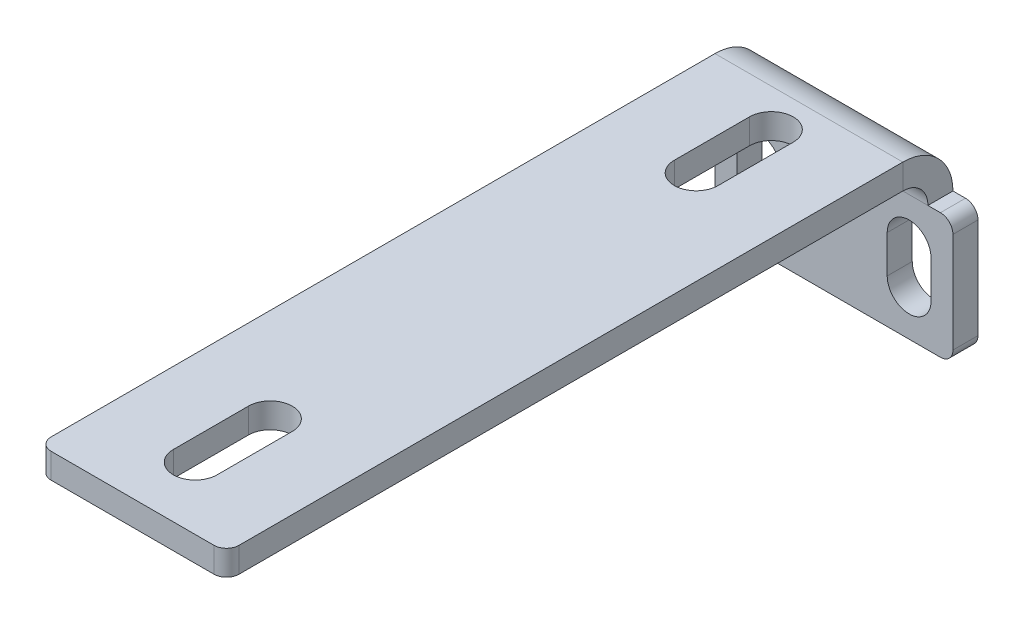
SolidWorks part; units mm, degrees
note: The reader was unsure of these and kept them because the rebuilt part matched: thickness of "Brida base1", "Brida de arista1", "Chapa metálica4", "Chapa metálica5", "Chapa metálica6"; flange length of "Brida de arista1".
material "aluminio"
ref_plane "Alzado" through (0, 0, 0) normal (0, 0, 1) x (1, 0, 0)
ref_plane "Planta" through (0, 0, 0) normal (0, 1, 0) x (1, 0, 0)
ref_plane "Vista lateral" through (0, 0, 0) normal (1, 0, 0) x (0, 0, -1)
sketch "Croquis1" plane through (0, 0, 0) normal (0, 0, 1) x (1, 0, 0)
  line L0 (0, -5) -> (9.5, -5) construction
  line L1 (0, 0) -> (19, 0)
  line L2 (0, 0) -> (0, -10)
  line L3 (0, -10) -> (19, -10)
  line L4 (19, 0) -> (19, -10)
  line L5 (9.5, 0) -> (9.5, -10) construction
  line L6 (3.5, -3.5) -> (3.5, -6.5) construction
  line L7 (5.25, -3.5) -> (5.25, -6.5)
  line L8 (1.75, -3.5) -> (1.75, -6.5)
  line L9 (15.5, -3.5) -> (15.5, -6.5) construction
  line L10 (17.25, -3.5) -> (17.25, -6.5)
  line L11 (13.75, -3.5) -> (13.75, -6.5)
  circle A0 centre (3.5, -5) radius 1.75 construction
  circle A1 centre (15.5, -5) radius 1.75 construction
  arc A2 (5.25, -3.5) -> (1.75, -3.5) centre (3.5, -3.5) ccw
  arc A3 (1.75, -6.5) -> (5.25, -6.5) centre (3.5, -6.5) ccw
  arc A4 (17.25, -3.5) -> (13.75, -3.5) centre (15.5, -3.5) ccw
  arc A5 (13.75, -6.5) -> (17.25, -6.5) centre (15.5, -6.5) ccw
  point P15 (3.5, -5)
  point P22 (15.5, -5)
  dimension "D1" = 3.5
  dimension "D2" = 3.5
  dimension "D3" = 12
  dimension "D4" = 5
  dimension "D6" = 3
  dimension "D5" = 1.75
base flange "Brida base1" sketch "Croquis1" thickness 2 reverse thickness direction no parameters "D1"=1
edge flange "Brida de arista1" sketch "Croquis8" flange angle 90 flange length 56 flange position bend outside bend radius 2 thickness 2 relief rectangular parameters "D6"=10
sketch "Croquis8" plane through (0, 0, 0) normal (0, 1, 0) x (-1, 0, 0)
  line L3 (-17, 56) -> (-2, 56)
  line L4 (-2, 0) -> (-2, 56)
  line L5 (-19, 0) -> (0, 0) construction
  line L6 (-9.5, 0) -> (-9.5, 39.9038) construction
  line L7 (-17, 0) -> (-2, 0)
  line L9 (-17, 0) -> (-17, 56)
  line L10 (-17, 0) -> (-9.5, 0) construction
  line L11 (-9.5, 0) -> (-2, 0) construction
  dimension "D1" = 15
  dimension "D2" = 56
bend "Pliegue de arista1" bend radius 2 bend angle 90 parameters "D5"=1
sketch "Croquis9" plane through (0, 4, 0) normal (0, 1, 0) x (1, 0, 0)
  line L0 (9.5, -11) -> (9.5, -5) construction
  line L1 (7.75, -11) -> (7.75, -5)
  line L2 (11.25, -11) -> (11.25, -5)
  line L3 (9.5, -31) -> (9.5, -25) construction
  line L4 (7.75, -31) -> (7.75, -25) construction
  line L5 (17, -2) -> (2, -2) construction
  line L6 (11.25, -31) -> (11.25, -25) construction
  line L7 (9.5, -51) -> (9.5, -45) construction
  line L8 (7.75, -51) -> (7.75, -45)
  line L9 (9.5, -2) -> (9.5, -5) construction
  line L10 (11.25, -51) -> (11.25, -45)
  arc A0 (7.75, -31) -> (11.25, -31) centre (9.5, -31) ccw construction
  arc A1 (11.25, -25) -> (7.75, -25) centre (9.5, -25) ccw construction
  arc A2 (7.75, -11) -> (11.25, -11) centre (9.5, -11) ccw
  arc A3 (11.25, -5) -> (7.75, -5) centre (9.5, -5) ccw
  arc A4 (7.75, -51) -> (11.25, -51) centre (9.5, -51) ccw
  arc A5 (11.25, -45) -> (7.75, -45) centre (9.5, -45) ccw
  point P6 (9.5, -28)
  point P10 (9.5, -8)
  point P22 (9.5, -48)
  dimension "D1" = 6
  dimension "D3" = 40
  dimension "D5" = 1.75
  dimension "D2" = 3
  dimension "D4" = 6
extrude "Cortar-Extruir1" cut sketch "Croquis9" against normal up to next normal cut yes
fillet "Redondeo1" radius 1 6 edges at (19, -10, -1) (0, -10, -1) (19, 0, -1) (0, 0, -1) (17, 3, 56) (2, 3, 56)
sketch "Líneas de pliegue1" [suppressed] plane through (0, 0, 0) normal (0, 1, 0) x (1, 0, 0)
sketch "Cuadro delimitador1" [suppressed] plane through (0, 0, 0) normal (0, 1, 0) x (1, 0, 0)
sheet metal parameters "Chapa metálica4" thickness 2 parameters "D1"=1, "D7"=1.5
flat pattern "Chapa desplegada4" [suppressed]
sketch "Líneas de pliegue2" plane through (0, 0, 0) normal (0, 1, 0) x (1, 0, 0)
sketch "Cuadro delimitador2" [suppressed] plane through (0, 0, 0) normal (0, 1, 0) x (1, 0, 0)
sheet metal parameters "Chapa metálica5" thickness 2 parameters "D1"=1
flat pattern "Chapa desplegada4" [suppressed]
sketch "Líneas de pliegue2" plane through (0, 0, 0) normal (0, 1, 0) x (1, 0, 0)
sketch "Cuadro delimitador2" [suppressed] plane through (0, 0, 0) normal (0, 1, 0) x (1, 0, 0)
bend of the flat pattern "Aplanar-<Pliegue de arista1>1"
sheet metal parameters "Chapa metálica6" thickness 2 parameters "D1"=1
flat pattern "Chapa desplegada4"
sketch "Líneas de pliegue2" plane through (0, 0, 0) normal (0, 0, 1) x (1, 0, 0)
  line L0 (17, 2.3562) -> (2, 2.3562) construction
  line L1 (17, 2.3562) -> (2, 2.3562) construction
sketch3d "Cuadro delimitador2" [suppressed]
  line L0 (19, 58.7124, 0) -> (19, -10, 0) construction
  line L1 (0, 58.7124, 0) -> (0, -10, 0) construction
  line L2 (19, 58.7124, 0) -> (0, 58.7124, 0) construction
  line L3 (19, -10, 0) -> (0, -10, 0) construction
bend of the flat pattern "Aplanar-<Pliegue de arista1>1"
